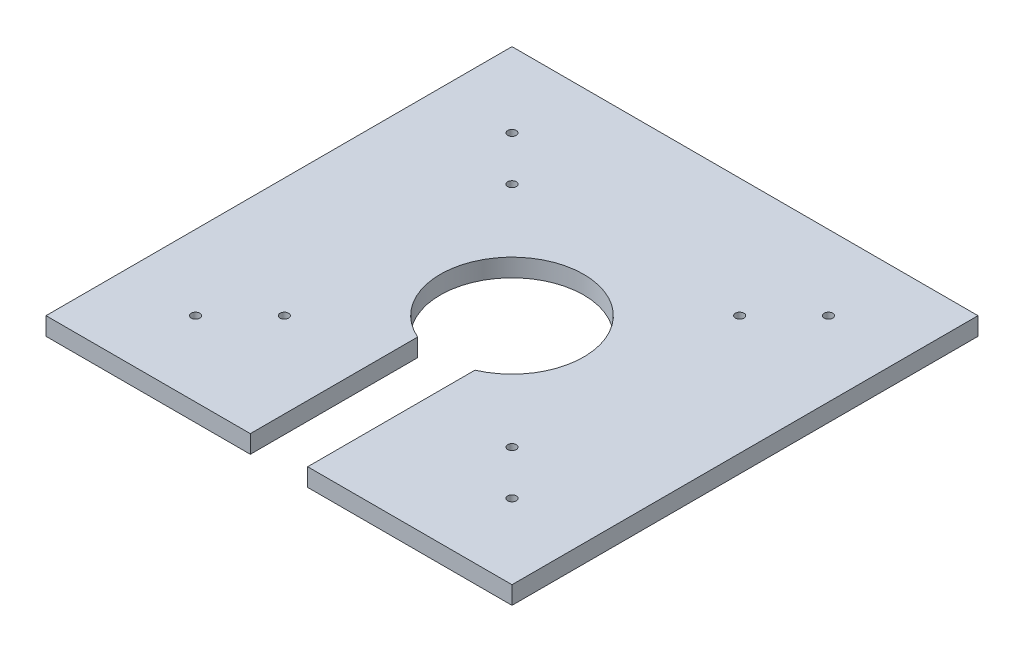
SolidWorks part; units mm, degrees
ref_plane "Front Plane" through (0, 0, 0) normal (0, 0, 1) x (1, 0, 0)
ref_plane "Top Plane" through (0, 0, 0) normal (0, 1, 0) x (1, 0, 0)
ref_plane "Right Plane" through (0, 0, 0) normal (1, 0, 0) x (0, 0, -1)
sketch "Sketch1" plane through (0, 0, 0) normal (0, 1, 0) x (1, 0, 0)
  line L0 (-33.0437, 65) -> (-33.0437, 0) construction
  line L1 (-98.0437, -65) -> (-41.0437, -65)
  line L2 (-98.0437, -65) -> (-98.0437, 65)
  line L3 (-98.0437, 65) -> (31.9563, 65)
  line L4 (31.9563, -65) -> (31.9563, 65)
  line L5 (-98.0437, -65) -> (31.9563, 65) construction
  line L6 (-98.0437, 65) -> (31.9563, -65) construction
  line L7 (-98.0437, 0) -> (-8, 0) construction
  line L8 (8, 0) -> (31.9563, 0) construction
  line L10 (-41.0437, -18.3303) -> (-41.0437, -65)
  line L12 (-25.0437, -18.3303) -> (-25.0437, -65)
  line L13 (-25.0437, -65) -> (31.9563, -65)
  circle A0 centre (-77.1861, 44.1423) radius 1.2
  circle A1 centre (-64.8014, 31.7577) radius 1.2
  circle A2 centre (-1.2861, 31.7577) radius 1.2
  circle A3 centre (11.0986, 44.1423) radius 1.2
  circle A4 centre (11.0986, -44.1423) radius 1.2
  circle A5 centre (-1.2861, -31.7577) radius 1.2
  circle A6 centre (-64.8014, -31.7577) radius 1.2
  circle A7 centre (-77.1861, -44.1423) radius 1.2
  arc A8 (-25.0437, -18.3303) -> (-41.0437, -18.3303) centre (-33.0437, 0) ccw
  point P0 (-33.0437, 0)
  point P31 (0, 0)
  point P33 (10.3894, -80.8673)
  dimension "D2" = 2.4
  dimension "D3" = 2.4
  dimension "D4" = 40
  dimension "D1" = 130
extrude "Boss-Extrude1" add sketch "Sketch1" along normal blind 5
